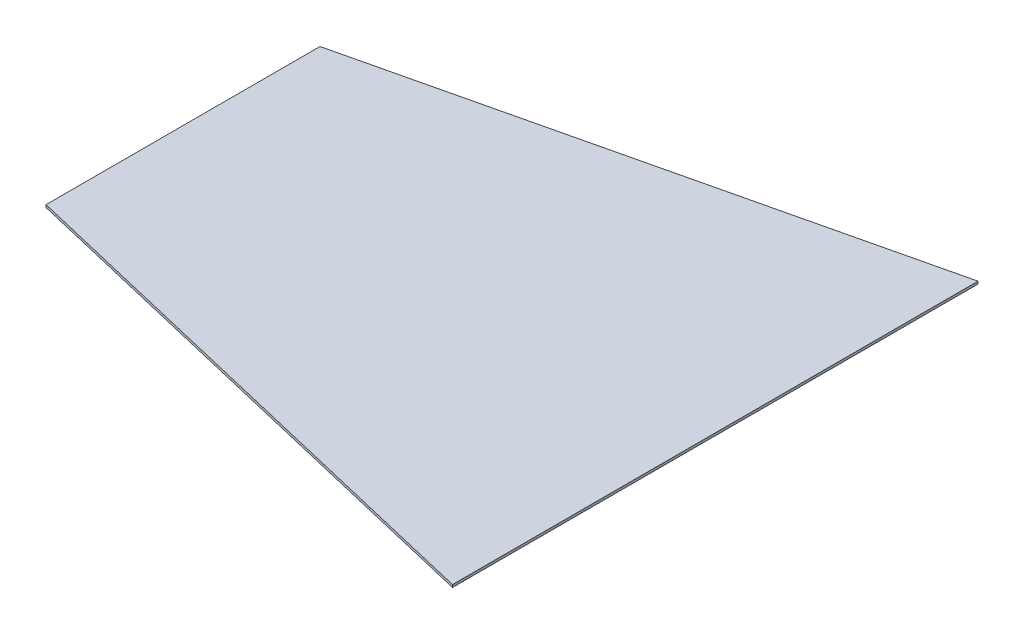
SolidWorks part; units mm, degrees
ref_plane "Front Plane" through (0, 0, 0) normal (0, 0, 1) x (1, 0, 0)
ref_plane "Top Plane" through (0, 0, 0) normal (0, 1, 0) x (1, 0, 0)
ref_plane "Right Plane" through (0, 0, 0) normal (1, 0, 0) x (0, 0, -1)
sketch "Sketch1" plane through (0, 0, 0) normal (0, 1, 0) x (1, 0, 0)
  line L1 (-429.1919, 61.4747) -> (296.4128, 61.4747)
  line L2 (-429.1919, 61.4747) -> (-429.1919, -466.8453)
  line L3 (-429.1919, -466.8453) -> (296.4128, -466.8453)
  line L4 (296.4128, 61.4747) -> (296.4128, -466.8453)
  dimension "D1" = 725.6047
  dimension "D2" = 528.32
extrude "Boss-Extrude1" add sketch "Sketch1" along normal blind 2.54
sketch "Sketch2" plane through (0, 2.54, 0) normal (0, 1, 0) x (1, 0, 0)
  line L0 (296.4128, -466.8453) -> (-429.1919, -295.3953)
  line L2 (-429.1919, 61.4747) -> (-429.1919, -466.8453) construction
  line L3 (-429.1919, -295.3953) -> (-429.1919, -466.8453)
  line L4 (-429.1919, -466.8453) -> (296.4128, -466.8453)
  line L5 (296.4128, 61.4747) -> (-429.1919, -109.9753)
  line L6 (-429.1919, -109.9753) -> (-429.1919, 61.4747)
  line L7 (296.4128, 61.4747) -> (-429.1919, 61.4747) construction
  line L8 (-429.1919, 61.4747) -> (296.4128, 61.4747)
  dimension "D1" = 171.45
  dimension "D2" = 171.45
extrude "Cut-Extrude1" cut sketch "Sketch2" against normal blind 2.54
sketch "Sketch5" plane through (0, 2.54, 0) normal (0, 1, 0) x (1, 0, 0)
  line L6 (-238.6919, -64.9629) -> (-429.1919, -109.9753)
  line L7 (-429.1919, -109.9753) -> (296.4128, 61.4747) construction
  line L8 (-429.1919, -109.9753) -> (-429.1919, -295.3953)
  line L9 (-429.1919, -295.3953) -> (-238.6919, -340.4078)
  line L10 (296.4128, -466.8453) -> (-429.1919, -295.3953) construction
  line L11 (-238.6919, -340.4078) -> (-238.6919, -64.9629)
  dimension "D1" = 190.5
extrude "Cut-Extrude4" cut sketch "Sketch5" against normal blind 2.54
